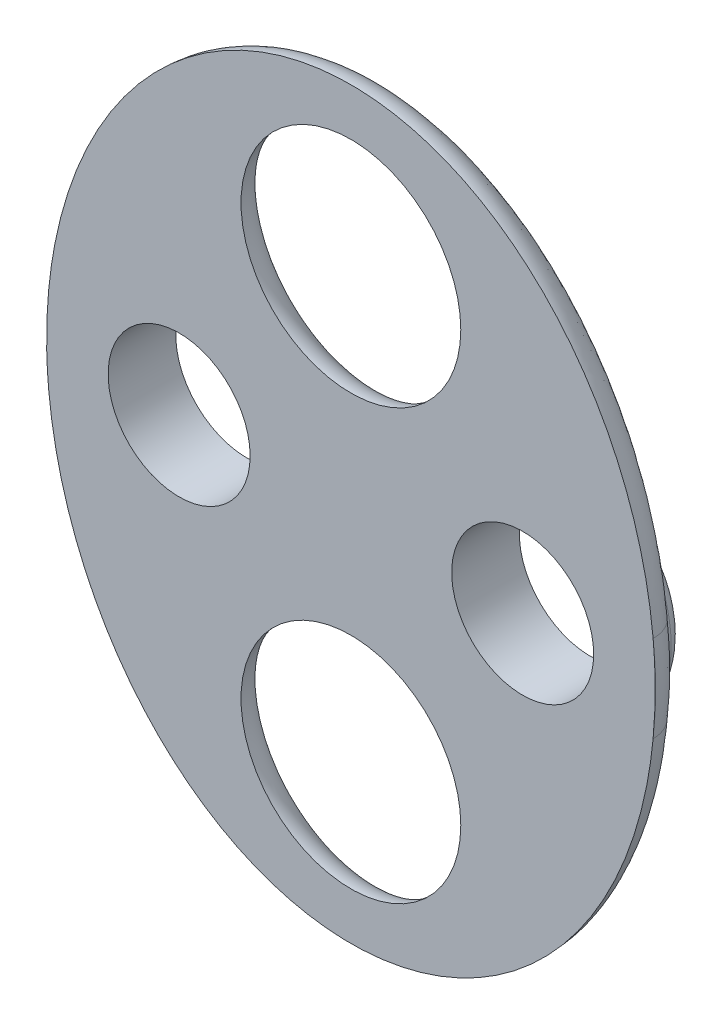
SolidWorks part; units mm, degrees
ref_plane "Plan de face" through (0, 0, 0) normal (0, 0, 1) x (1, 0, 0)
ref_plane "Plan de dessus" through (0, 0, 0) normal (0, 1, 0) x (1, 0, 0)
ref_plane "Plan de droite" through (0, 0, 0) normal (1, 0, 0) x (0, 0, -1)
sketch "Esquisse1" plane through (0, 0, 0) normal (0, 0, 1) x (1, 0, 0)
  ellipse E0 centre (0, 0) end of major axis (0, 11) minor radius 9
  dimension "D1" = 22
  dimension "D2" = 18
extrude "Boss.-Extru.1" add sketch "Esquisse1" along normal blind 1
sketch "Esquisse4" plane through (0, 0, 0) normal (0, 0, 1) x (1, 0, 0)
  line L0 (-5.08, 0) -> (5.08, 0) construction
  circle A0 centre (-5.08, 0) radius 3.1
  circle A1 centre (5.08, 0) radius 3.1
  dimension "D2" = 6.2
  dimension "D1" = 10.16
extrude "Boss.-Extru.2" add sketch "Esquisse4" against normal blind 1
sketch "Esquisse2" plane through (0, 0, 1) normal (0, 0, 1) x (1, 0, 0)
  line L0 (-5.08, 0) -> (5.08, 0) construction
  line L1 (0, 6.35) -> (0, -6.35) construction
  circle A0 centre (-5.08, 0) radius 2.1
  circle A1 centre (5.08, 0) radius 2.1
  circle A2 centre (0, 6.35) radius 3.25
  circle A3 centre (0, -6.35) radius 3.25
  dimension "D2" = 4.2
  dimension "D4" = 6.5
  dimension "D1" = 10.16
  dimension "D3" = 12.7
extrude "Enlèv. mat.-Extru.1" cut sketch "Esquisse2" against normal through all
fillet "Congé1" radius 1 2 edges at (-1.98, 0, -1) (8.18, 0, -1)
fillet "Congé2" radius 1 3 edges at (0, 11, 0) (3.25, -6.35, 0) (3.25, 6.35, 0)
fillet "Congé3" radius 1 4 edges at (-8.18, 0, 0) (8.18, 0, 0) (-1.98, 0, 0) (1.98, 0, 0)
